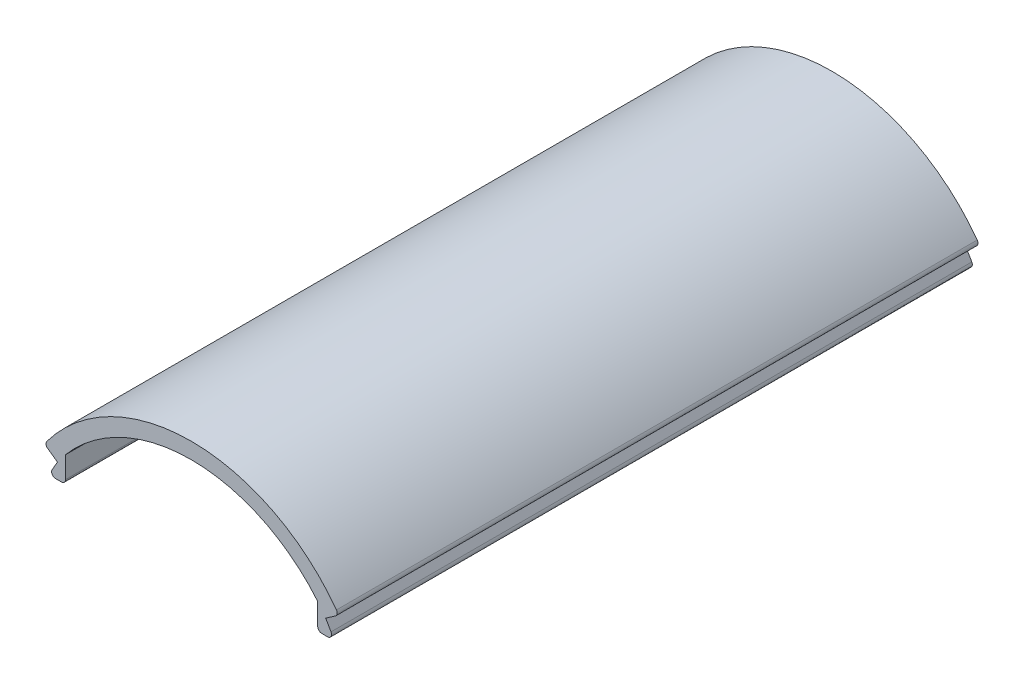
SolidWorks part; units mm, degrees
ref_plane "Front Plane" through (0, 0, 0) normal (0, 0, 1) x (1, 0, 0)
ref_plane "Top Plane" through (0, 0, 0) normal (0, 1, 0) x (1, 0, 0)
ref_plane "Right Plane" through (0, 0, 0) normal (1, 0, 0) x (0, 0, -1)
sketch "Sketch1" plane through (0, 0, 0) normal (0, 0, 1) x (1, 0, 0)
  circle A0 centre (0, 0) radius 22.5
  circle A1 centre (0, 0) radius 20.5
  dimension "D1" = 45
  dimension "D2" = 41
extrude "Boss-Extrude1" add sketch "Sketch1" along normal blind 80
sketch "Sketch2" plane through (0, 0, 80) normal (0, 0, 1) x (1, 0, 0)
  line L1 (-22.5, 0) -> (22.5, 0)
  line L2 (-22.5, 0) -> (-22.5, 22.5)
  line L3 (-22.5, 22.5) -> (22.5, 22.5)
  line L4 (22.5, 0) -> (22.5, 22.5)
  circle A0 centre (0, 0) radius 22.5 construction
extrude "Cut-Extrude1" cut sketch "Sketch2" against normal through all
sketch "Sketch4" plane through (0, 0, 80) normal (0, 0, 1) x (1, 0, 0)
  line L0 (19.1831, 11.7583) -> (18.4309, 12.9055)
  line L1 (16.7926, 11.7583) -> (18.4309, 12.9055)
  line L3 (20.5, 0) -> (22.5, 0)
  line L4 (16.7926, 11.7583) -> (19.1831, 11.7583)
  line L5 (18.4309, 12.9055) -> (16.7926, 11.7583)
  line L6 (15.7926, 11.7583) -> (15.7926, 9.7583)
  line L7 (19.1831, 11.7583) -> (14.7926, 11.7583)
  line L8 (19.1831, 11.7583) -> (19.1831, 8.7583)
  line L9 (19.1831, 8.7583) -> (14.7926, 8.7583)
  line L10 (14.7926, 11.7583) -> (14.7926, 8.7583)
  line L11 (15.7926, 9.7583) -> (18.0285, 9.7583)
  line L12 (16.7926, 11.7583) -> (15.7926, 11.7583)
  line L13 (14.7926, 8.7583) -> (18.5349, 8.7583)
  line L14 (14.7926, 8.7583) -> (14.7926, 11.7583)
  line L15 (14.7926, 11.7583) -> (16.7926, 11.7583)
  line L16 (-16.7023, 11.8863) -> (-18.3406, 13.0335)
  line L17 (-22.5, 0) -> (-20.5, 0) construction
  line L18 (-16.7023, 11.8863) -> (-15.7023, 11.8863)
  line L19 (-19.1041, 11.8863) -> (-14.7023, 11.8863)
  line L20 (-19.1041, 11.8863) -> (-19.1041, 8.8863)
  line L21 (-19.1041, 8.8863) -> (-14.7023, 8.8863)
  line L22 (-14.7023, 11.8863) -> (-14.7023, 8.8863)
  line L23 (-14.7023, 11.8863) -> (-15.7023, 11.8863)
  line L24 (-14.7023, 11.8863) -> (-14.7023, 8.8863)
  line L25 (-14.7023, 8.8863) -> (-15.7023, 8.8863)
  line L26 (-15.7023, 11.8863) -> (-15.7023, 8.8863)
  line L27 (-19.1041, 8.8863) -> (-14.7023, 8.8863)
  line L28 (-19.1041, 8.8863) -> (-19.1041, 9.8863)
  line L29 (-19.1041, 9.8863) -> (-14.7023, 9.8863)
  line L30 (-14.7023, 8.8863) -> (-14.7023, 9.8863)
  line L31 (-15.7023, 11.8863) -> (-15.7023, 9.8863)
  line L32 (-15.7023, 9.8863) -> (-17.9586, 9.8863)
  line L33 (-16.7023, 11.8863) -> (-15.7023, 11.1746)
  line L34 (-15.7023, 11.1746) -> (-15.7023, 9.8863)
  line L35 (-15.7023, 9.8863) -> (-17.9586, 9.8863)
  line L36 (-16.7023, 11.8863) -> (-19.1041, 11.8863)
  line L37 (-19.1041, 11.8863) -> (-19.1041, 8.8863)
  line L38 (-19.1041, 8.8863) -> (-18.4739, 8.8863)
  line L39 (-22.5, 0) -> (-20.5, 0)
  line L40 (-16.7023, 11.8863) -> (-15.7023, 11.8863)
  line L41 (-15.7023, 9.8863) -> (-17.9586, 9.8863)
  arc A0 (22.5, 0) -> (18.4309, 12.9055) centre (0, 0) ccw
  arc A1 (20.5, 0) -> (16.7926, 11.7583) centre (0, 0) ccw
  arc A2 (18.0285, 9.7583) -> (16.7926, 11.7583) centre (0, 0) ccw
  arc A3 (18.5349, 8.7583) -> (16.7926, 11.7583) centre (0, 0) ccw
  arc A4 (-22.5, 0) -> (-18.3406, 13.0335) centre (0, 0) cw
  arc A5 (-20.5, 0) -> (-16.7023, 11.8863) centre (0, 0) cw
  arc A6 (-17.9586, 9.8863) -> (-16.7023, 11.8863) centre (0, 0) cw
  arc A7 (-18.4739, 8.8863) -> (-16.7023, 11.8863) centre (0, 0) cw
  arc A8 (-17.9586, 9.8863) -> (-16.7023, 11.8863) centre (0, 0) cw
  line M11 (22.5, 0) -> (20.5, 0)
  dimension "D1" = 35
  dimension "D7" = 35
  dimension "D2" = 2
  dimension "D3" = 3
  dimension "D4" = 2
  dimension "D5" = 1
  dimension "D6" = 1
  dimension "D8" = 3
  dimension "D9" = 1
  dimension "D10" = 1
  dimension "D11" = 1
extrude "Boss-Extrude2" add sketch "Sketch4" against normal up to surface (80 mm away) separate body contours A1 A0 L8 L9 M11 | L1 L4 L0 | A1 L9 L8 L4 | L9 A1 L11 L6 L7 L10 | L16 A4 L39 A5 | L28 L27 L30 L29 | L24 L23 L26 L25 region at (18.1356, 12.1407, 80) region at (18.3654, 10.5555, 80) region at (20.7342, 5.0849, 80) region at (15.7447, 10.7583, 80) up to face at (0, -10.75, 0)
sketch "Sketch5" plane through (0, 0, 80) normal (0, 0, 1) x (1, 0, 0)
  line L0 (16.7926, 11.7583) -> (18.4309, 12.9055) construction
  line L1 (-16.7023, 11.8863) -> (-18.3406, 13.0335) construction
  line L2 (16.7926, 11.7583) -> (18.4309, 12.9055)
  line L3 (-18.3406, 13.0335) -> (-16.7023, 11.8863)
  line L4 (-15.7023, 9.9863) -> (-17.7992, 9.9863)
  line L5 (-15.7023, 11.8863) -> (-15.7023, 9.8863) construction
  line L6 (-17.7992, 9.9863) -> (-16.7023, 11.8863)
  line L7 (-15.7023, 11.8863) -> (-15.7023, 9.9863)
  line L8 (-15.7023, 11.8863) -> (-16.7023, 11.8863)
  line L9 (-17.9586, 9.8863) -> (-15.7023, 9.8863) construction
  line L10 (-15.7023, 11.8863) -> (-16.7023, 11.8863)
  line L11 (-15.7023, 11.8863) -> (-15.7023, 13.8432)
  line L12 (-15.7023, 13.8432) -> (-16.7023, 13.8432)
  line L13 (-16.7023, 11.8863) -> (-16.7023, 13.8432)
  line L14 (16.7926, 11.7583) -> (15.7926, 11.7583)
  line L15 (15.7926, 11.7583) -> (15.7926, 9.7583) construction
  line L16 (15.7926, 11.7583) -> (15.7926, 9.8583)
  line L17 (15.7926, 9.8583) -> (17.8896, 9.8583)
  line L18 (17.8896, 9.8583) -> (16.7926, 11.7583)
  line L19 (15.7926, 9.7583) -> (18.0285, 9.7583) construction
  line L21 (15.7926, 11.7583) -> (16.7926, 11.7583)
  line L22 (15.7926, 11.7583) -> (15.7926, 14.392)
  line L23 (15.7926, 14.392) -> (16.7926, 14.392)
  line L24 (16.7926, 11.7583) -> (16.7926, 14.392)
  arc A0 (-16.7023, 11.8863) -> (16.7926, 11.7583) centre (0, 0) cw
  arc A1 (-18.3406, 13.0335) -> (18.4309, 12.9055) centre (0, 0) cw
  arc A2 (-18.3406, 13.0335) -> (-22.5, 0) centre (0, 0) ccw construction
  line M14 (18.4309, 12.9055) -> (16.7926, 11.7583)
  line M17 (15.7926, 9.7583) -> (15.7926, 11.7583)
  dimension "D1" = 60
  dimension "D2" = 0.1
  dimension "D3" = 60
  dimension "D4" = 0.1
extrude "Boss-Extrude3" add sketch "Sketch5" against normal up to surface (80 mm away) contours A1 L3 L13 L12 L11 A0 L22 L23 L24 M14 | A0 L22 L14 | L22 A0 L24 L23 | L17 L18 L14 M17 | L7 L8 L6 L4 | A0 L8 L11 | L13 A0 L11 L12 region at (17.1757, 13.0751, 80) region at (16.5992, 10.6962, 80) region at (16.3484, 13.3758, 80) region at (16.1306, 12.2018, 80) region at (-16.2855, 13.143, 80) region at (-16.0402, 12.3231, 80) region at (-16.5089, 10.8241, 80) up to face at (17.8607, 8.848, 0)
sketch "Sketch6" plane through (0, 0, 80) normal (0, 0, 1) x (1, 0, 0)
  line L0 (18.5349, 8.7583) -> (14.7926, 8.7583) construction
  line L1 (14.7926, 11.7583) -> (15.7926, 11.7583)
  line L2 (14.7926, 11.7583) -> (14.7926, 8.7583)
  line L3 (14.7926, 8.7583) -> (15.7926, 8.7583)
  line L4 (15.7926, 11.7583) -> (15.7926, 8.7583)
  line L5 (-16.7023, 11.8863) -> (-18.3318, 13.0459)
  line L6 (15.7926, 9.7583) -> (19.1614, 9.7583)
  line L7 (15.7926, 9.7583) -> (15.7926, 8.7583)
  line L8 (15.7926, 8.7583) -> (19.1614, 8.7583)
  line L9 (19.1614, 9.7583) -> (19.1614, 8.7583)
  line L10 (-14.7023, 8.8863) -> (-15.7023, 8.8863)
  line L11 (-14.7023, 8.8863) -> (-14.7023, 11.8863)
  line L12 (-14.7023, 11.8863) -> (-15.7023, 11.8863)
  line L13 (-15.7023, 8.8863) -> (-15.7023, 11.8863)
  line L14 (-15.7023, 9.8863) -> (-19.4266, 9.8863)
  line L15 (-15.7023, 9.8863) -> (-15.7023, 8.8863)
  line L16 (-15.7023, 8.8863) -> (-19.4266, 8.8863)
  line L17 (-19.4266, 9.8863) -> (-19.4266, 8.8863)
  line L18 (16.7926, 11.7583) -> (18.4309, 12.9055)
  arc A0 (-16.7023, 11.8863) -> (16.7926, 11.7583) centre (0, 0) ccw
  arc A1 (18.4309, 12.9055) -> (-22.5, 0) centre (0, 0) ccw construction
  arc A2 (18.4309, 12.9055) -> (-18.3318, 13.0459) centre (0, 0) cw
  line M1 (-14.7023, 11.8863) -> (-15.7023, 11.8863)
  line M5 (15.7926, 11.7583) -> (14.7926, 11.7583)
  line M6 (14.7926, 11.7583) -> (14.7926, 8.7583)
  line M7 (14.7926, 8.7583) -> (18.5349, 8.7583)
  arc M8 (18.5349, 8.7583) -> (20.5, 0) centre (0, 0) cw
  line M9 (20.5, 0) -> (22.5, 0)
  arc M10 (22.5, 0) -> (19.1831, 11.7583) centre (0, 0) ccw
  line M11 (19.1831, 11.7583) -> (18.4309, 12.9055)
  arc M12 (18.4309, 12.9055) -> (-22.5, 0) centre (0, 0) ccw
  line M13 (-22.5, 0) -> (-20.5, 0)
  arc M14 (-20.5, 0) -> (-18.4739, 8.8863) centre (0, 0) cw
  line M15 (-18.4739, 8.8863) -> (-14.7023, 8.8863)
  line M16 (-14.7023, 8.8863) -> (-14.7023, 11.8863)
  line M18 (-15.7023, 9.9863) -> (-15.7023, 9.8863)
  line M19 (-15.7023, 9.8863) -> (-17.9586, 9.8863)
  arc M20 (-17.9586, 9.8863) -> (-16.7023, 11.8863) centre (0, 0) cw
  arc M23 (16.7926, 11.7583) -> (18.0285, 9.7583) centre (0, 0) cw
  line M24 (18.0285, 9.7583) -> (15.7926, 9.7583)
  line M25 (15.7926, 9.7583) -> (15.7926, 9.8583)
extrude "Cut-Extrude2" cut sketch "Sketch6" against normal through all contours L17 L14 L5 L16 M20 M12 M13 M14 | A2 A0 M9 M13 | A0 L14 L17 L16 | A0 L13 M19 M15 | L13 M15 M16 M1 M18 | L4 M5 M6 M7 M25 | A0 L4 M7 M24 | A0 L8 L9 L6 | L18 L6 L9 L8 M23 M8 M9 M10 M11 region at (15.2926, 10.2583, 80) region at (17.0443, 9.2414, 80) region at (18.7121, 9.3066, 80) region at (20.254, 6.2663, 80) region at (21.5, -0.5031, 80) region at (-20.234, 6.3031, 80) region at (-16.9665, 9.3693, 80) region at (-18.8151, 9.4219, 80) region at (-15.2023, 10.3863, 80)
fillet "Fillet1" radius 0.5 6 edges at (-15.7023, 9.9863, 40) (-17.7992, 9.9863, 40) (-18.3318, 13.0459, 40) (18.4309, 12.9055, 40) (15.7926, 9.8583, 40) (17.8896, 9.8583, 40)
